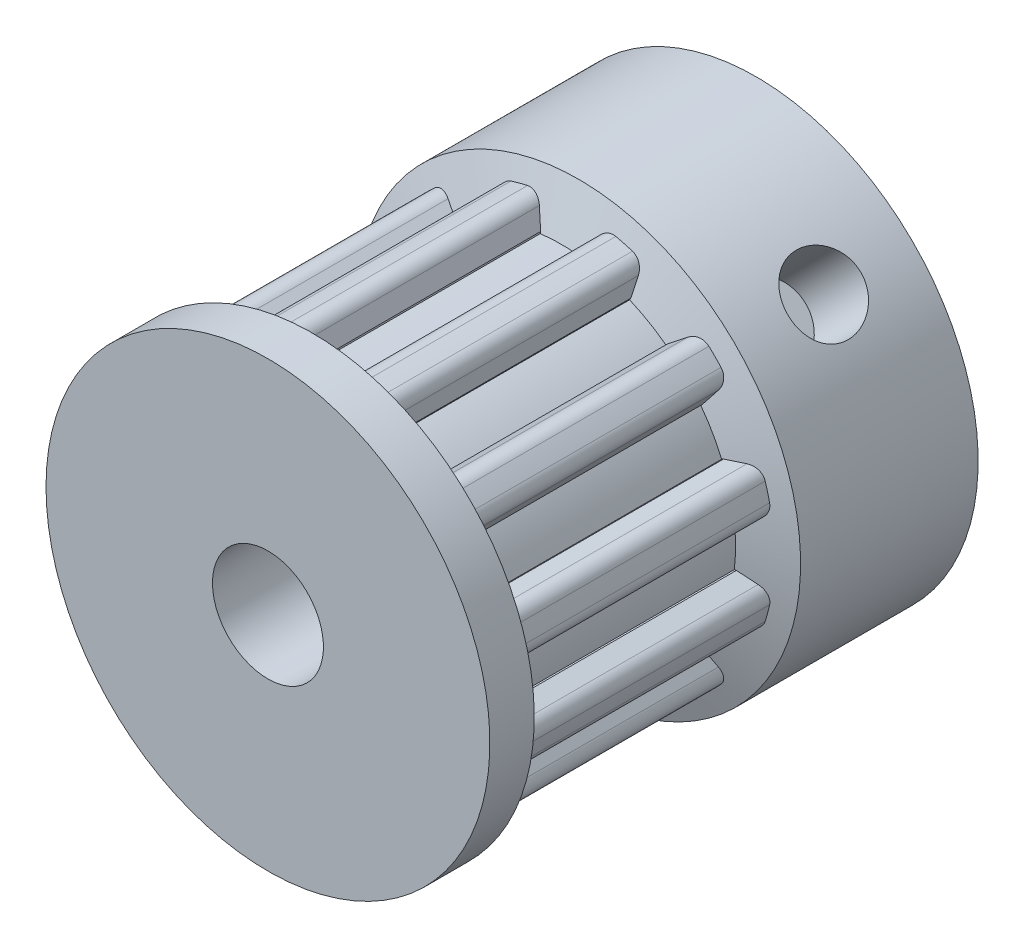
SolidWorks part; units mm, degrees
ref_plane "Front Plane" through (0, 0, 0) normal (0, 0, 1) x (1, 0, 0)
ref_plane "Top Plane" through (0, 0, 0) normal (0, 1, 0) x (1, 0, 0)
ref_plane "Right Plane" through (0, 0, 0) normal (1, 0, 0) x (0, 0, -1)
sketch "Sketch2" plane through (0, 0, 0) normal (0, 1, 0) x (1, 0, 0)
  line L0 (0, 0) -> (0, -25.2491) construction
  line L1 (2.5, 0) -> (2.5, -22)
  line L2 (2.5, -22) -> (10, -22)
  line L3 (10, -22) -> (10, -20)
  line L4 (10, -20) -> (7.8525, -19.2184)
  line L5 (7.8525, -19.2184) -> (7.8525, -8.7816)
  line L6 (7.8525, -8.7816) -> (10, -8)
  line L7 (10, -8) -> (10, 0)
  line L8 (10, 0) -> (2.5, 0)
  dimension "D1" = 5
  dimension "D2" = 20
  dimension "D3" = 8
  dimension "D4" = 12
  dimension "D5" = 2
  dimension "D6" = 15.705
  dimension "D7" = 40
revolve "Revolve1" add sketch "Sketch2" angle 360 about L0
sketch "Sketch3" plane through (0, 0, 22) normal (0, 0, 1) x (1, 0, 0)
  line L1 (4.7585, 6.3315) -> (1.502, 1.9985)
  line L2 (1.9985, 1.502) -> (6.3315, 4.7585)
  line L3 (0, 0) -> (15.9441, 0) construction
  line L4 (6.4612, 6.4612) -> (1.7678, 1.7678) construction
  line L6 (5.4002, 6.7809) -> (4.7585, 6.3315)
  line L7 (6.3315, 4.7585) -> (6.7809, 5.4002)
  line L8 (4.7585, 6.3315) -> (6.3315, 4.7585) construction
  arc A3 (6.1815, 6.7292) -> (5.4002, 6.7809) centre (5.7587, 6.2689) ccw
  arc A4 (6.7292, 6.1815) -> (6.1815, 6.7292) centre (0, 0) ccw
  arc A5 (6.7809, 5.4002) -> (6.7292, 6.1815) centre (6.2689, 5.7587) ccw
  circle A6 centre (0, 0) radius 2.5 construction
  arc A7 (1.9985, 1.502) -> (1.502, 1.9985) centre (0, 0) ccw
  dimension "D1" = 9.1375
  dimension "D3" = 0.625
  dimension "D2" = 16.147
  dimension "D4" = 20
  dimension "D5" = 45
  dimension "D6" = 7.8418
extrude "Boss-Extrude1" add sketch "Sketch3" against normal up to surface (22 mm away) up to face at (-2.5, 0, 0)
pattern_circular "CirPattern1" count 12 over 360 about axis through (0, 0, 0) along (0, 0, -1) of "Boss-Extrude1"
ref_plane "Plane1" through (0, 0, 0) normal (0.7071, 0.7071, 0) x (-0.7071, 0.7071, 0)
sketch "Sketch4" plane through (0, 0, 0) normal (0.7071, 0.7071, 0) x (-0.7071, 0.7071, 0)
  line L0 (0, 22) -> (0, 0) construction
  line L1 (-10, 0) -> (10, 0) construction
  circle A0 centre (0, 4) radius 1.65
  dimension "D1" = 3.3
  dimension "D2" = 4
extrude "Cut-Extrude1" cut sketch "Sketch4" against normal through all and the other way through all
sketch "Sketch5" plane through (0, 0, 0) normal (0.7071, 0.7071, 0) x (-0.7071, 0.7071, 0)
  line L0 (-3.5, 0) -> (-3.5, 6.0207)
  line L1 (-10, 0) -> (10, 0) construction
  line L2 (-3.5, 6.0207) -> (0, 8.0415)
  line L3 (0, 19.2184) -> (0, 8.7816) construction
  line L4 (0, 22) -> (0, 0) construction
  line L5 (0, 8.0415) -> (3.5, 6.0207)
  line L6 (3.5, 6.0207) -> (3.5, 0)
  line L7 (3.5, 0) -> (-3.5, 0)
  dimension "D1" = 7
  dimension "D2" = 3.5
  dimension "D3" = 60
extrude "Cut-Extrude2" cut sketch "Sketch5" against normal blind 3 from offset 3.5 offset against normal yes
pattern_circular "CirPattern2" count 2 over 360 about axis through (0, 0, 0) along (0, 0, -1) of "Cut-Extrude2"
